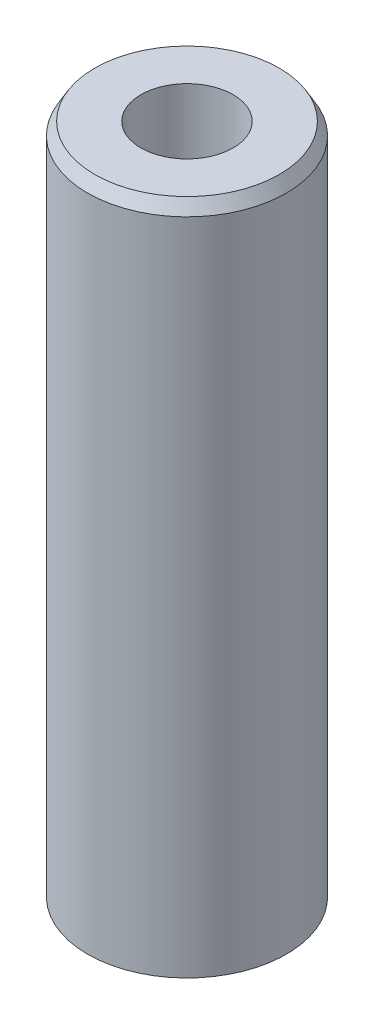
SolidWorks part; units mm, degrees
ref_plane "Front Plane" through (0, 0, 0) normal (0, 0, 1) x (1, 0, 0)
ref_plane "Top Plane" through (0, 0, 0) normal (0, 1, 0) x (1, 0, 0)
ref_plane "Right Plane" through (0, 0, 0) normal (1, 0, 0) x (0, 0, -1)
sketch "Sketch1" plane through (0, 0, 0) normal (0, 1, 0) x (1, 0, 0)
  circle A0 centre (0, 0) radius 35
  dimension "SHAFT_OD" = 70
extrude "Boss-Extrude1" add sketch "Sketch1" along normal blind 238.9645
sketch "Sketch2" plane through (0, 0, 0) normal (0, 1, 0) x (1, 0, 0)
  circle A0 centre (0, 0) radius 16.2447
  dimension "BORE_D" = 32.4893
extrude "Cut-Extrude1" cut sketch "Sketch2" along normal through all
chamfer "Chamfer1" distance 4.3907 angle 30 2 edges at (0, 238.9645, 35) (0, 0, 35) first distance on face at (0, 238.9645, 35) first distance on face at (0, 0, 16.2447)
